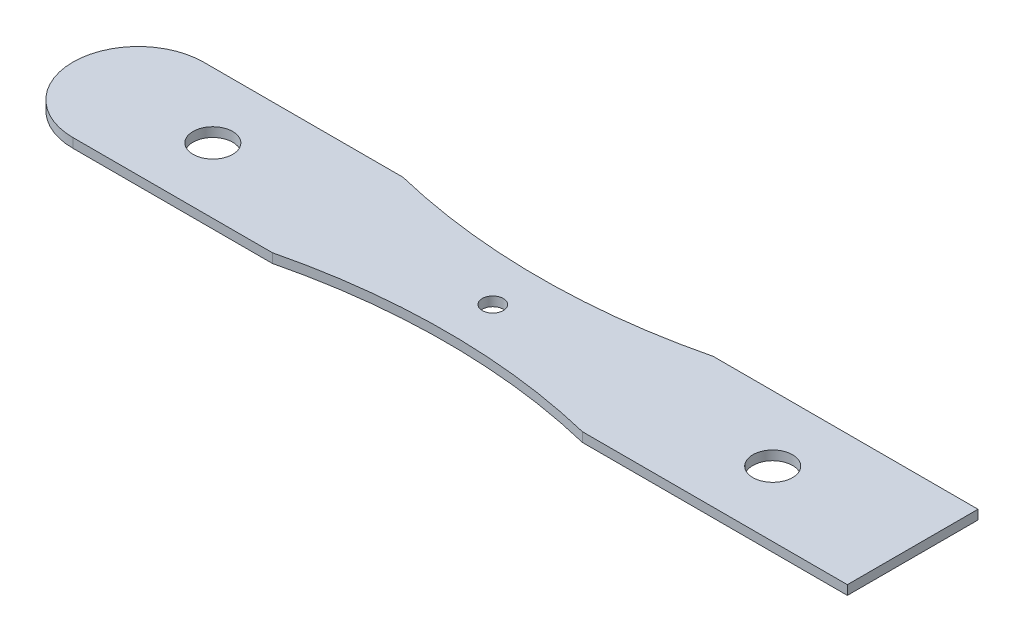
SolidWorks part; units mm, degrees
ref_plane "前视" through (0, 0, 0) normal (0, 0, 1) x (1, 0, 0)
ref_plane "上视" through (0, 0, 0) normal (0, 1, 0) x (1, 0, 0)
ref_plane "右视" through (0, 0, 0) normal (1, 0, 0) x (0, 0, -1)
sketch "草图1" plane through (0, 0, 0) normal (0, 1, 0) x (1, 0, 0)
  line L1 (-90, 14) -> (90, 14)
  line L2 (-90, 14) -> (-90, -14)
  line L3 (-90, -14) -> (90, -14)
  line L4 (90, 14) -> (90, -14)
  line L5 (-90, 14) -> (90, -14) construction
  line L6 (-90, -14) -> (90, 14) construction
  point P0 (0, 0)
  dimension "D1" = 180
  dimension "D2" = 28
extrude "凸台-拉伸1" add sketch "草图1" along normal blind 2 contours L2 | L2 | L3 L1 | L4 | L4 region at (0, 0, 0)
sketch "草图2" plane through (0, 2, 0) normal (0, 1, 0) x (1, 0, 0)
  circle A0 centre (-60, 0) radius 4.25
  circle A1 centre (60, 0) radius 4.25
  circle A2 centre (0, 0) radius 2.25
  dimension "D1" = 8.5
  dimension "D2" = 8.5
  dimension "D5" = 4.5
  dimension "D3" = 120
  dimension "D4" = 60
extrude "切除-拉伸1" cut sketch "草图2" against normal up to next
fillet "圆角1" 2 edges at (-90, 1, 14) (-90, 1, -14) type full round first side face at (0, 1, 14) second side face at (0, 1, -14) middle face at (-90, 1, 0)
sketch "草图3" plane through (0, 2, 0) normal (0, 1, 0) x (1, 0, 0)
  circle A0 centre (-78.5, 0) radius 2.25
  circle A1 centre (-41.5, 0) radius 2.25
  circle A2 centre (41.5, 0) radius 2.25
  circle A3 centre (78.5, 0) radius 2.25
  circle A4 centre (-60, 0) radius 4.25 construction
  circle A5 centre (60, 0) radius 4.25 construction
  dimension "D2" = 18.5
  dimension "D3" = 4.5
  dimension "D4" = 4.5
  dimension "D6" = 18.5
  dimension "D7" = 4.5
  dimension "D8" = 4.5
  dimension "D1" = 37
  dimension "D5" = 37
extrude "切除-拉伸2" [suppressed] cut sketch "草图3" against normal up to next
sketch "草图4" plane through (0, 2, 0) normal (0, 1, 0) x (1, 0, 0)
  circle A0 centre (0, 150) radius 140
  dimension "D2" = 280
  dimension "D1" = 150
extrude "切除-拉伸3" cut sketch "草图4" against normal up to next
mirror "镜向1" about plane through (0, 0, 0) normal (0, 0, 1) of "切除-拉伸3"
